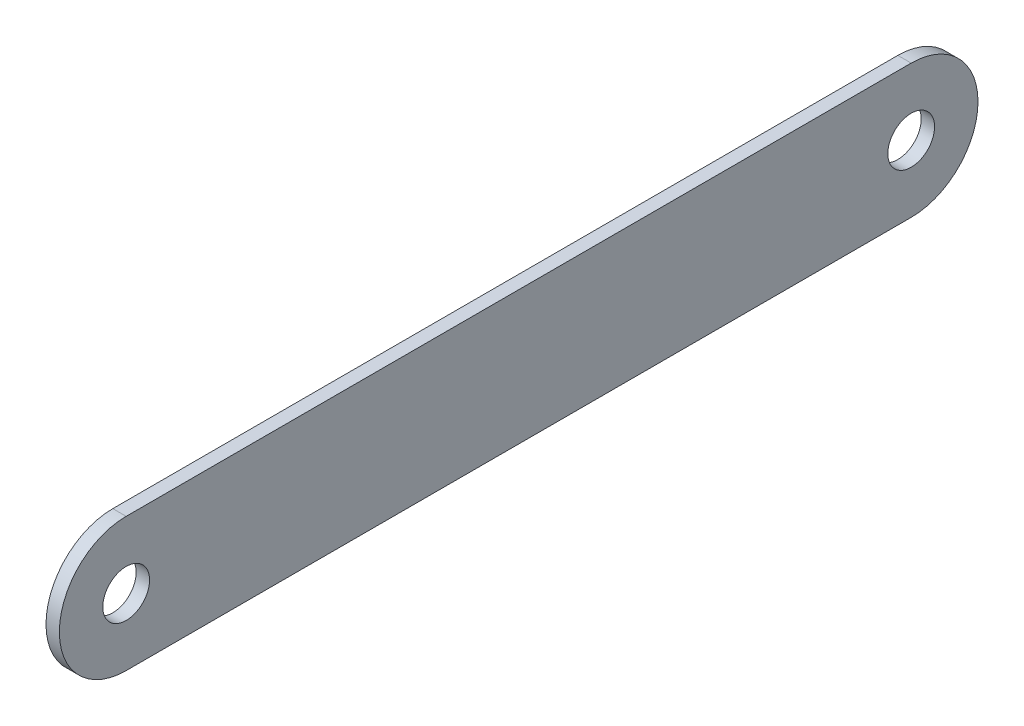
SolidWorks part; units mm, degrees
ref_plane "Спереди" through (0, 0, 0) normal (0, 0, 1) x (1, 0, 0)
ref_plane "Сверху" through (0, 0, 0) normal (0, 1, 0) x (1, 0, 0)
ref_plane "Справа" through (0, 0, 0) normal (1, 0, 0) x (0, 0, -1)
sketch "Эскиз1" plane through (0, 0, 0) normal (1, 0, 0) x (0, 0, -1)
  line L0 (0, 0) -> (235, 0) construction
  line L1 (0, 20) -> (235, 20)
  line L2 (0, -20) -> (235, -20)
  circle A0 centre (0, 0) radius 7
  arc A1 (0, 20) -> (0, -20) centre (0, 0) ccw
  circle A2 centre (235, 0) radius 7
  arc A3 (235, -20) -> (235, 20) centre (235, 0) ccw
  dimension "D2" = 14
  dimension "D3" = 40
  dimension "D1" = 235
base flange "Базовая кромка1" sketch "Эскиз1" thickness 4 reverse thickness direction no parameters "D1"=1.5
sketch "Сгиб-Линии1" [suppressed] plane through (0, 0, 0) normal (0, 1, 0) x (1, 0, 0)
sketch "Граничная рамка1" [suppressed] plane through (0, 0, 0) normal (0, 1, 0) x (1, 0, 0)
sheet metal parameters "Листовой металл3" thickness 4 parameters "D1"=1.5
flat pattern "Развертка3" [suppressed]
sketch "Сгиб-Линии2" plane through (0, 0, 0) normal (0, 1, 0) x (1, 0, 0)
sketch3d "Граничная рамка2" [suppressed]
  line L0 (-20, -20, 0) -> (255, -20, 0) construction
  line L1 (-20, 20, 0) -> (255, 20, 0) construction
  line L2 (-20, -20, 0) -> (-20, 20, 0) construction
  line L3 (255, -20, 0) -> (255, 20, 0) construction
